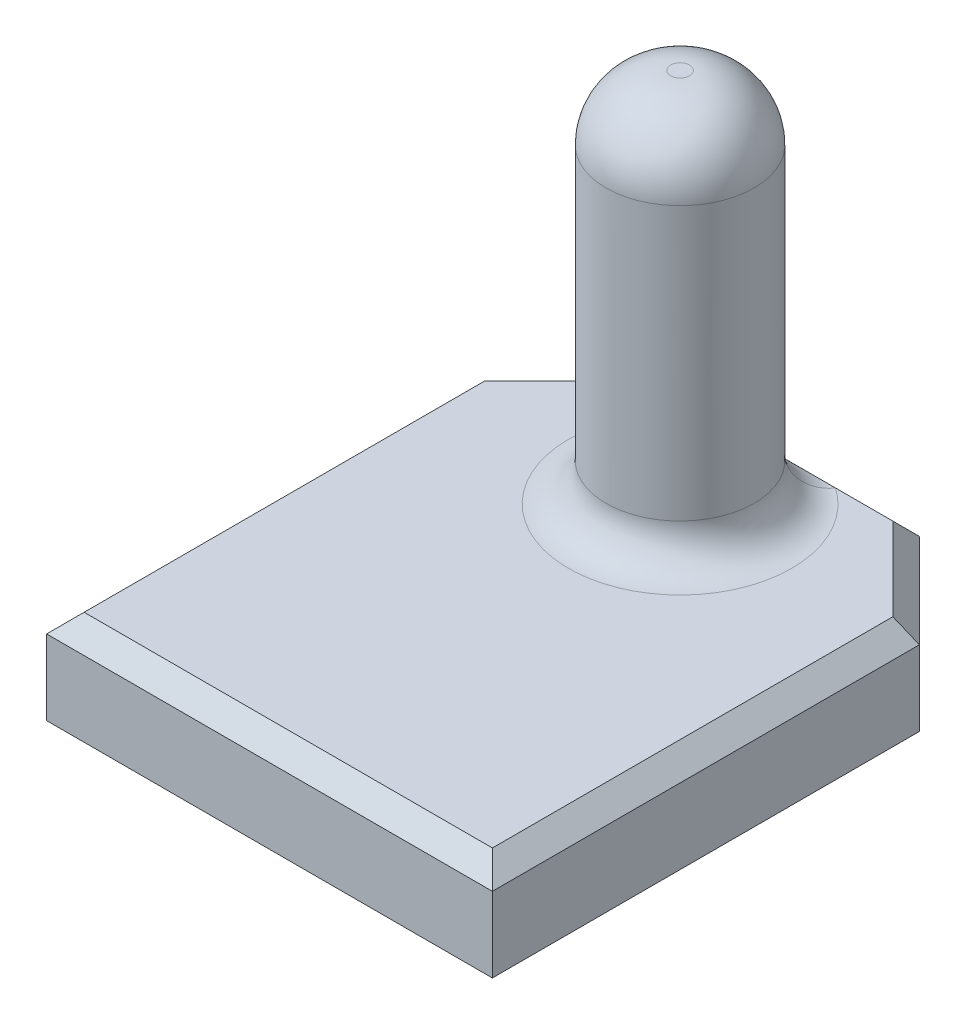
SolidWorks part; units mm, degrees
ref_plane "Front Plane" through (0, 0, 0) normal (0, 0, 1) x (1, 0, 0)
ref_plane "Top Plane" through (0, 0, 0) normal (0, 1, 0) x (1, 0, 0)
ref_plane "Right Plane" through (0, 0, 0) normal (1, 0, 0) x (0, 0, -1)
sketch "Sketch1" plane through (0, 0, 0) normal (0, 1, 0) x (1, 0, 0)
  line L0 (-11.875, 8.875) -> (-6.875, 13.875)
  line L1 (-11.875, -13.875) -> (11.875, -13.875)
  line L2 (-11.875, -13.875) -> (-11.875, 8.875)
  line L3 (-6.875, 13.875) -> (6.875, 13.875)
  line L4 (11.875, -13.875) -> (11.875, 8.875)
  line L5 (-11.875, -13.875) -> (11.875, 13.875) construction
  line L6 (-11.875, 13.875) -> (11.875, -13.875) construction
  line L7 (11.875, 8.875) -> (6.875, 13.875)
  line L8 (-11.875, 8.875) -> (-11.875, 13.875) construction
  line L9 (-11.875, 13.875) -> (-6.875, 13.875) construction
  line L10 (6.875, 13.875) -> (11.875, 13.875) construction
  line L11 (11.875, 8.875) -> (11.875, 13.875) construction
  point P0 (0, 0)
  dimension "D1" = 23.75
  dimension "D2" = 27.75
  dimension "D3" = 5
  dimension "D4" = 5
extrude "Main Body Extrude" add sketch "Sketch1" along normal blind 5
chamfer "Body Entry Chamfer" distance 1 angle 45 6 edges at (11.875, 5, 2.5) (0, 5, 13.875) (-11.875, 5, 2.5) (0, 5, -13.875) (-9.375, 5, -11.375) (9.375, 5, -11.375)
sketch "Sketch2" plane through (0, 5, 0) normal (0, 1, 0) x (1, 0, 0)
  circle A0 centre (0, 8) radius 3.95
  dimension "D1" = 7.9
  dimension "D2" = 8
extrude "Pin Extrude" add sketch "Sketch2" along normal blind 20
fillet "Pin Top Fillet" radius 3.45 1 edges at (0, 25, -4.05)
fillet "Pin Base Fillet" radius 2 1 edges at (0, 5, -11.95)
